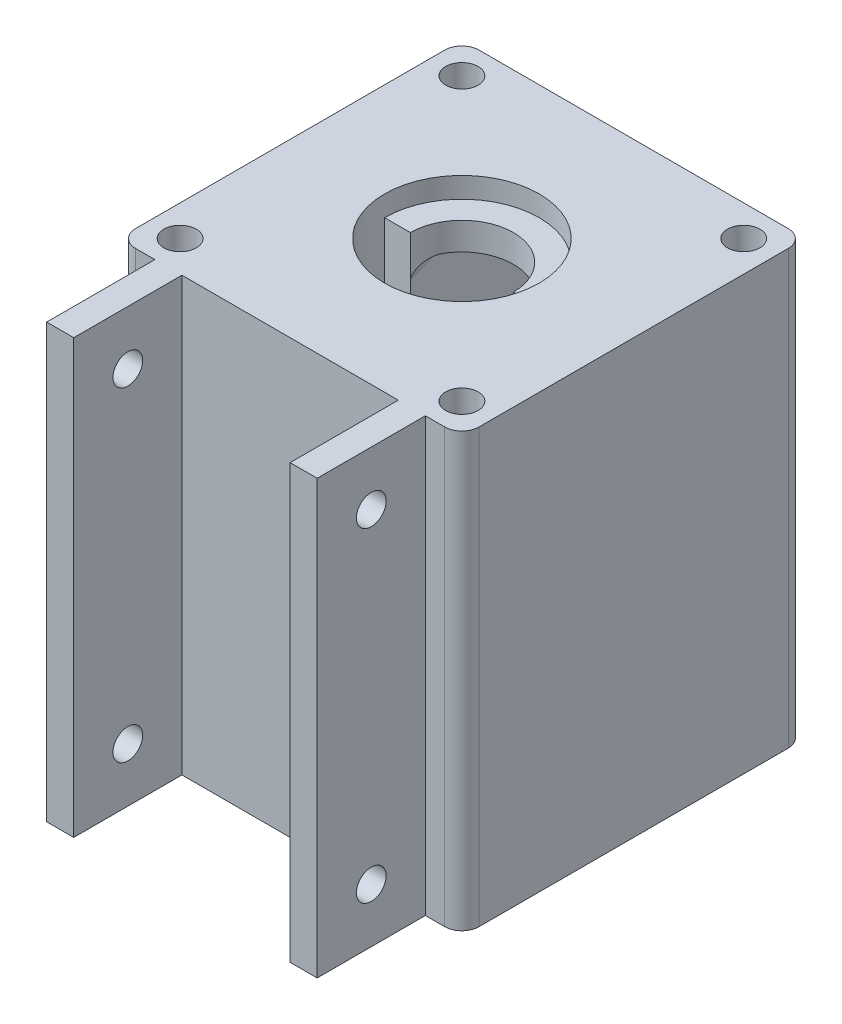
SolidWorks part; units mm, degrees
ref_plane "Front" through (0, 0, 0) normal (0, 0, 1) x (1, 0, 0)
ref_plane "Top" through (0, 0, 0) normal (0, 1, 0) x (1, 0, 0)
ref_plane "Right" through (0, 0, 0) normal (1, 0, 0) x (0, 0, -1)
sketch "Sketch2" plane through (0, 0, 0) normal (0, 1, 0) x (1, 0, 0)
  line L1 (-31.75, 31.75) -> (31.75, 31.75)
  line L2 (-31.75, 31.75) -> (-31.75, -31.75)
  line L3 (-31.75, -31.75) -> (31.75, -31.75)
  line L4 (31.75, 31.75) -> (31.75, -31.75)
  line L5 (-31.75, 31.75) -> (31.75, -31.75) construction
  line L6 (-31.75, -31.75) -> (31.75, 31.75) construction
  point P0 (0, 0)
  dimension "D1" = 63.5
  dimension "D2" = 63.5
extrude "Boss-Extrude1" add sketch "Sketch2" along normal blind 80
sketch "Sketch3" plane through (0, 80, 0) normal (0, 1, 0) x (1, 0, 0)
  line L0 (9.525, 0) -> (14.2875, 0)
  line L1 (-9.525, 0) -> (-14.2875, 0)
  arc A0 (9.525, 0) -> (-9.525, 0) centre (0, 0) ccw
  arc A1 (-14.2875, 0) -> (14.2875, 0) centre (0, 0) ccw
  dimension "D1" = 28.575
  dimension "D2" = 19.05
extrude "Cut-Extrude1" cut sketch "Sketch3" against normal up to next
fillet "Fillet1" radius 3.175 4 edges at (31.75, 40, -31.75) (31.75, 40, 31.75) (-31.75, 40, 31.75) (-31.75, 40, -31.75)
sketch "Sketch4" plane through (0, 80, 0) normal (0, 1, 0) x (1, 0, 0)
  circle A0 centre (0, 0) radius 14.2875
extrude "Cut-Extrude2" cut sketch "Sketch4" against normal blind 3.81
ref_plane "Plane1" through (0, 71.11, 0) normal (0, 1, 0) x (1, 0, 0)
sketch "Sketch6" plane through (0, 71.11, 0) normal (0, 1, 0) x (1, 0, 0)
  line L0 (0, 0) -> (0, 31.75) construction
  line L1 (28.575, 31.75) -> (-28.575, 31.75) construction
  line L2 (9.525, 0) -> (19.05, 31.75)
  line L3 (19.05, 31.75) -> (-19.05, 31.75)
  line L4 (31.75, -28.575) -> (31.75, 28.575) construction
  line L5 (-9.525, 0) -> (-19.05, 31.75)
  arc A0 (9.525, 0) -> (-9.525, 0) centre (0, 0) ccw construction
  arc A1 (9.525, 0) -> (-9.525, 0) centre (0, 0) ccw
  dimension "D1" = 12.7
extrude "Cut-Extrude3" cut sketch "Sketch6" against normal offset from surface (62.22 mm away) 8.89 up to face at (0, 0, 1.1906)
sketch "Sketch7" plane through (0, 0, 0) normal (1, 0, 0) x (0, 0, -1)
  line L0 (0, 8.89) -> (31.75, 8.89) construction
  line L1 (0, 8.89) -> (31.75, 8.89)
  line L2 (0, 8.89) -> (0, 0)
  line L3 (0, 0) -> (31.75, 8.89)
extrude "Cut-Extrude4" cut sketch "Sketch7" against normal up to surface and the other way up to surface up to face at (-14.2875, 40, -15.875) other way up to face at (14.2875, 40, -15.875)
sketch "Sketch8" plane through (0, 0, -31.75) normal (0, 0, -1) x (-1, 0, 0)
  line L0 (0, 80) -> (0, 0) construction
  line L1 (-28.575, 80) -> (28.575, 80) construction
  line L2 (28.575, 40) -> (-28.575, 40) construction
  line L3 (28.575, 0) -> (28.575, 80) construction
  line L4 (-28.575, 80) -> (-28.575, 0) construction
  circle A0 centre (-23.575, 65) radius 3
  circle A1 centre (23.575, 65) radius 3
  circle A2 centre (23.575, 15) radius 3
  circle A3 centre (-23.575, 15) radius 3
  dimension "D1" = 6
  dimension "D2" = 5
  dimension "D3" = 15
fillet "Fillet2" radius 2.54 5 edges at (14.2875, 71.11, -15.875) (-14.2875, 71.11, -15.875) (0, 2.667, -9.525) (-14.2875, 4.445, -15.875) (14.2875, 4.445, -15.875)
sketch "Sketch9" plane through (0, 0, 31.75) normal (0, 0, 1) x (1, 0, 0)
  line L0 (0, 80) -> (0, 0) construction
  line L1 (-28.575, 80) -> (28.575, 80) construction
  line L2 (-28.575, 0) -> (28.575, 0) construction
  line L3 (-20, 80) -> (-25, 80)
  line L4 (-20, 80) -> (-20, 0)
  line L5 (-20, 0) -> (-25, 0)
  line L6 (-25, 80) -> (-25, 0)
  line L7 (-20, 80) -> (-25, 0) construction
  line L8 (-20, 0) -> (-25, 80) construction
  line L9 (20, 0) -> (25, 80) construction
  line L10 (20, 80) -> (25, 0) construction
  line L11 (25, 80) -> (25, 0)
  line L12 (20, 0) -> (25, 0)
  line L13 (20, 80) -> (20, 0)
  line L14 (20, 80) -> (25, 80)
  point P9 (-22.5, 40)
  point P16 (22.5, 40)
  dimension "D1" = 5
  dimension "D2" = 20
extrude "Boss-Extrude2" add sketch "Sketch9" along normal blind 20
sketch "Sketch10" plane through (-25, 0, 0) normal (-1, 0, 0) x (0, 0, 1)
  line L0 (41.75, 80) -> (41.75, 0) construction
  line L1 (51.75, 80) -> (31.75, 80) construction
  line L2 (51.75, 0) -> (31.75, 0) construction
  circle A0 centre (41.75, 70) radius 2.75
  circle A1 centre (41.75, 10) radius 2.75
  dimension "D1" = 5.5
  dimension "D2" = 10
  dimension "D3" = 10
extrude "Cut-Extrude6" cut sketch "Sketch10" against normal through all
sketch "Sketch11" plane through (0, 0, 0) normal (0, -1, 0) x (1, 0, 0)
  circle A0 centre (26.0427, -26.0427) radius 3
  circle A1 centre (26.0427, 26.0427) radius 3
  circle A2 centre (-26.0427, -26.0427) radius 3
  circle A3 centre (-26.0427, 26.0427) radius 3
  dimension "D1" = 6
extrude "Cut-Extrude7" cut sketch "Sketch11" against normal blind 10
sketch "Sketch12" plane through (0, 80, 0) normal (0, 1, 0) x (1, 0, 0)
  circle A0 centre (26.0427, -26.0427) radius 3 construction
  circle A1 centre (26.0427, 26.0427) radius 3 construction
  circle A2 centre (-26.0427, 26.0427) radius 3 construction
  circle A3 centre (-26.0427, -26.0427) radius 3 construction
  circle A4 centre (26.0427, -26.0427) radius 3
  circle A5 centre (26.0427, 26.0427) radius 3
  circle A6 centre (-26.0427, 26.0427) radius 3
  circle A7 centre (-26.0427, -26.0427) radius 3
extrude "Cut-Extrude8" cut sketch "Sketch12" against normal blind 10
extrude "Cut-Extrude9" cut sketch "Sketch8" against normal blind 10
